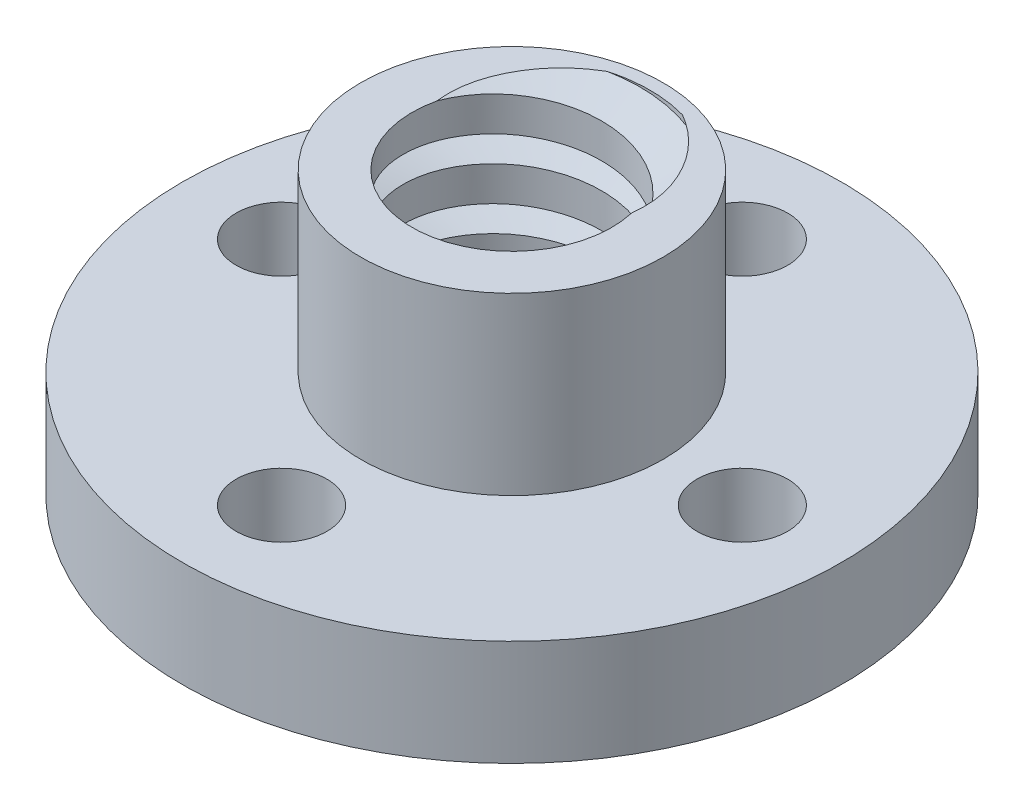
SolidWorks part; units mm, degrees
ref_plane "Alzado" through (0, 0, 0) normal (0, 0, 1) x (1, 0, 0)
ref_plane "Planta" through (0, 0, 0) normal (0, 1, 0) x (1, 0, 0)
ref_plane "Vista lateral" through (0, 0, 0) normal (1, 0, 0) x (0, 0, -1)
sketch "Croquis1" plane through (0, 0, 0) normal (0, 0, 1) x (1, 0, 0)
  line L0 (0, -38.4924) -> (0, -43.4924) construction
  line L1 (-48.7583, 0) -> (43.2974, 0) construction
  line L2 (-5, -1.2057) -> (-5, 0)
  line L3 (-5, 0) -> (-10.9, 0)
  line L4 (-10.9, 0) -> (-10.9, 3.5)
  line L5 (-10.9, 3.5) -> (-5, 3.5)
  line L6 (-5, 3.5) -> (-5, 9.2943)
  line L7 (-5, 9.2943) -> (-3.3, 9.2943)
  line L8 (-3.3, 9.2943) -> (-3.3, -1.2057)
  line L9 (-3.3, -1.2057) -> (-5, -1.2057)
  dimension "D1" = 1.7
  dimension "D2" = 3.5
  dimension "D3" = 10.5
  dimension "D4" = 5.9
  dimension "D5" = 5
revolve "Revolución1" add sketch "Croquis1" angle 360 about L0
sketch "Croquis3" plane through (0, 3.5, 0) normal (0, 1, 0) x (1, 0, 0)
  circle A0 centre (0, 7.62) radius 1.5
  circle A1 centre (7.62, 0) radius 1.5
  circle A2 centre (0, -7.62) radius 1.5
  circle A3 centre (-7.62, 0) radius 1.5
  point P12 (0, 0)
  dimension "D3" = 3
  dimension "D1" = 7.62
  dimension "D2" = 4
extrude "Cortar-Extruir1" cut sketch "Croquis3" against normal through all
ref_plane "Plano1" through (0, 19.2943, 0) normal (0, 1, 0) x (1, 0, 0)
sketch "Croquis4" plane through (0, 19.2943, 0) normal (0, 1, 0) x (1, 0, 0)
  circle A0 centre (0, 0) radius 3.3 construction
  circle A1 centre (0, 0) radius 3.3
curve "Hélice/Espiral1" pitch 2 height 30 radius 3.3 centre (0, 19.2943, 0) axis (0, -1, 0) start towards (-1, 0, 0)
sketch "Croquis5" plane through (0, 0, 0) normal (0, 0, 1) x (1, 0, 0)
  line L0 (3.0698, 19.2841) -> (3.0698, 18.3041)
  line L1 (3.0698, 18.3041) -> (4.5698, 18.706)
  line L2 (4.5698, 18.706) -> (4.5698, 18.8822)
  line L3 (4.5698, 18.8822) -> (3.0698, 19.2841)
  dimension "D1" = 0.98
  dimension "D2" = 1.5
  dimension "D3" = 75
sweep "Cortar-Barrer1" cut profiles "Croquis5" path "Hélice/Espiral1"
